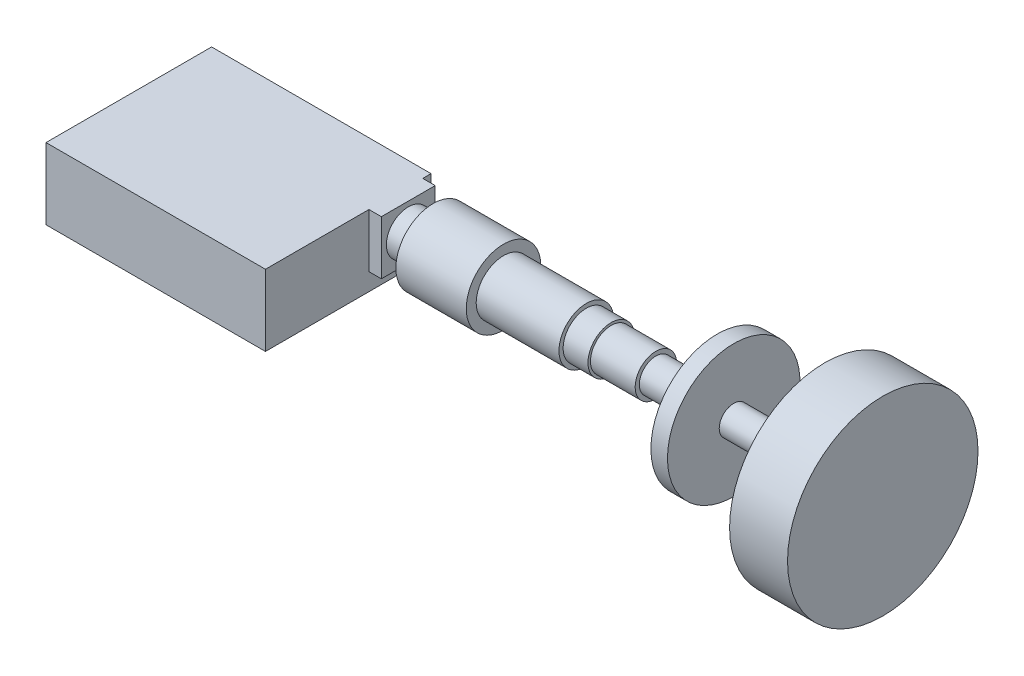
SolidWorks part; units mm, degrees
ref_plane "Front Plane" through (0, 0, 0) normal (0, 0, 1) x (1, 0, 0)
ref_plane "Top Plane" through (0, 0, 0) normal (0, 1, 0) x (1, 0, 0)
ref_plane "Right Plane" through (0, 0, 0) normal (1, 0, 0) x (0, 0, -1)
sketch "Sketch1" plane through (0, 0, 0) normal (0, 1, 0) x (1, 0, 0)
  line L1 (-13.25, -10) -> (13.25, -10)
  line L2 (-13.25, -10) -> (-13.25, 10)
  line L3 (-13.25, 10) -> (13.25, 10)
  line L4 (13.25, -10) -> (13.25, 10)
  line L5 (0, 10) -> (0, -10) construction
  line L6 (-13.25, 0) -> (13.25, 0) construction
  point P0 (0, 0)
  dimension "D1" = 20
  dimension "D2" = 26.5
extrude "Boss-Extrude1" add sketch "Sketch1" along normal blind 8.6
sketch "Sketch2" plane through (13.25, 0, 0) normal (1, 0, 0) x (0, 0, -1)
  line L0 (2.5, 8.6) -> (9, 8.6)
  line L1 (2.5, 8.6) -> (2.5, 2.1)
  line L2 (9, 8.6) -> (9, 2.1)
  line L3 (2.5, 2.1) -> (9, 2.1)
  line L4 (-10, 8.6) -> (10, 8.6) construction
  line L5 (10, 8.6) -> (10, 0) construction
  dimension "D1" = 6.5
  dimension "D2" = 1
extrude "Boss-Extrude2" add sketch "Sketch2" along normal blind 1.5
sketch "Sketch3" plane through (14.75, 0, 0) normal (1, 0, 0) x (0, 0, -1)
  line L0 (5.75, 8.6) -> (5.75, 2.1) construction
  line L1 (9, 8.6) -> (2.5, 8.6) construction
  line L2 (2.5, 2.1) -> (9, 2.1) construction
  circle A0 centre (5.75, 5.35) radius 2.65
  dimension "D1" = 5.3
ref_plane "Plane1" through (0, 0, -5.75) normal (0, 0, 1) x (1, 0, 0)
sketch "Sketch6" plane through (0, 0, -5.75) normal (0, 0, 1) x (1, 0, 0)
  line L0 (14.75, 5.35) -> (60.5073, 5.35) construction
  line L1 (14.75, 2.7) -> (14.75, 8) construction
  line L2 (14.75, 5.35) -> (14.75, 2.7)
  line L3 (14.75, 2.7) -> (17.75, 2.7)
  line L4 (17.75, 2.7) -> (17.75, 0.85)
  line L5 (17.75, 0.85) -> (26.25, 0.85)
  line L6 (26.25, 0.85) -> (26.25, 2.05)
  line L7 (26.25, 2.05) -> (36.25, 2.05)
  line L8 (36.25, 2.05) -> (36.25, 2.55)
  line L9 (36.25, 2.55) -> (39.25, 2.55)
  line L10 (39.25, 2.55) -> (39.25, 2.85)
  line L11 (39.25, 2.85) -> (44.65, 2.85)
  line L12 (44.65, 2.85) -> (44.65, 3.35)
  line L13 (44.65, 3.35) -> (52.05, 3.35)
  line L14 (52.05, 3.35) -> (52.05, -2.65)
  line L15 (52.05, -2.65) -> (54.05, -2.65)
  line L16 (54.05, -2.65) -> (54.05, 3.6)
  line L17 (54.05, 3.6) -> (65.05, 3.6)
  line L18 (65.05, 3.6) -> (65.05, -6.15)
  line L19 (65.05, -6.15) -> (72.05, -6.15)
  line L20 (72.05, -6.15) -> (72.05, 5.35)
  line L21 (72.05, 5.35) -> (14.75, 5.35)
  point P4 (16.25, 2.7)
  dimension "D1" = 2.65
  dimension "D2" = 3
  dimension "D3" = 4.5
  dimension "D4" = 8.5
  dimension "D5" = 3.3
  dimension "D6" = 10
  dimension "D7" = 2.8
  dimension "D8" = 3
  dimension "D9" = 2.5
  dimension "D10" = 5.4
  dimension "D11" = 2
  dimension "D12" = 7.4
  dimension "D13" = 2
  dimension "D14" = 8
  dimension "D15" = 1.75
  dimension "D16" = 7
  dimension "D17" = 11.5
  dimension "D18" = 11
revolve "Revolve1" add sketch "Sketch6" angle 360 about L0
sketch "Sketch8" plane through (0, 0, 0) normal (0, 0, 1) x (1, 0, 0)
  line L0 (26.25, 0.85) -> (26.25, 9.85) construction
  line L1 (26.25, 0.85) -> (26.25, 9.85) construction
  line L2 (26.25, 5.35) -> (8.6196, 5.35) construction
  line L3 (-13.25, 4.3) -> (13.25, 4.3) construction
  line L7 (-13.25, 0) -> (13.25, 0)
  line L8 (13.25, 0) -> (13.25, 8.6)
  line L9 (13.25, 8.6) -> (-13.25, 8.6)
  line L10 (-13.25, 8.6) -> (-13.25, 0)
  line L11 (-13.25, 0) -> (13.25, 0)
  line L12 (13.25, 0) -> (13.25, 8.6)
  line L13 (13.25, 8.6) -> (-13.25, 8.6)
  line L14 (-13.25, 8.6) -> (-13.25, 0)
  dimension "D1" = 0
